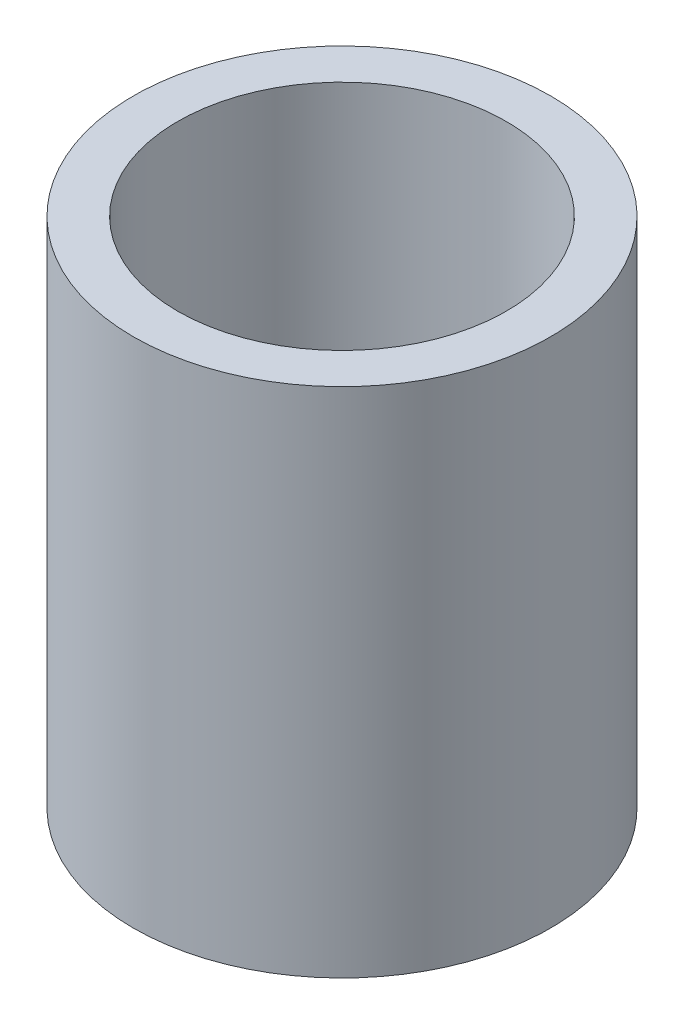
SolidWorks part; units mm, degrees
ref_plane "Front Plane" through (0, 0, 0) normal (0, 0, 1) x (1, 0, 0)
ref_plane "Top Plane" through (0, 0, 0) normal (0, 1, 0) x (1, 0, 0)
ref_plane "Right Plane" through (0, 0, 0) normal (1, 0, 0) x (0, 0, -1)
sketch "Sketch1" plane through (0, 0, 0) normal (0, 1, 0) x (1, 0, 0)
  circle A0 centre (0, 0) radius 17.5
  dimension "SLEEVE_OD" = 35
extrude "Boss-Extrude1" add sketch "Sketch1" along normal blind 42.9564
sketch "Sketch2" plane through (0, 0, 0) normal (0, 1, 0) x (1, 0, 0)
  circle A0 centre (0, 0) radius 13.785
  dimension "BORE_D" = 27.5701
extrude "Cut-Extrude1" cut sketch "Sketch2" along normal through all
chamfer "Chamfer1" distance 3.2304 angle 27.253 rebuild error yes
